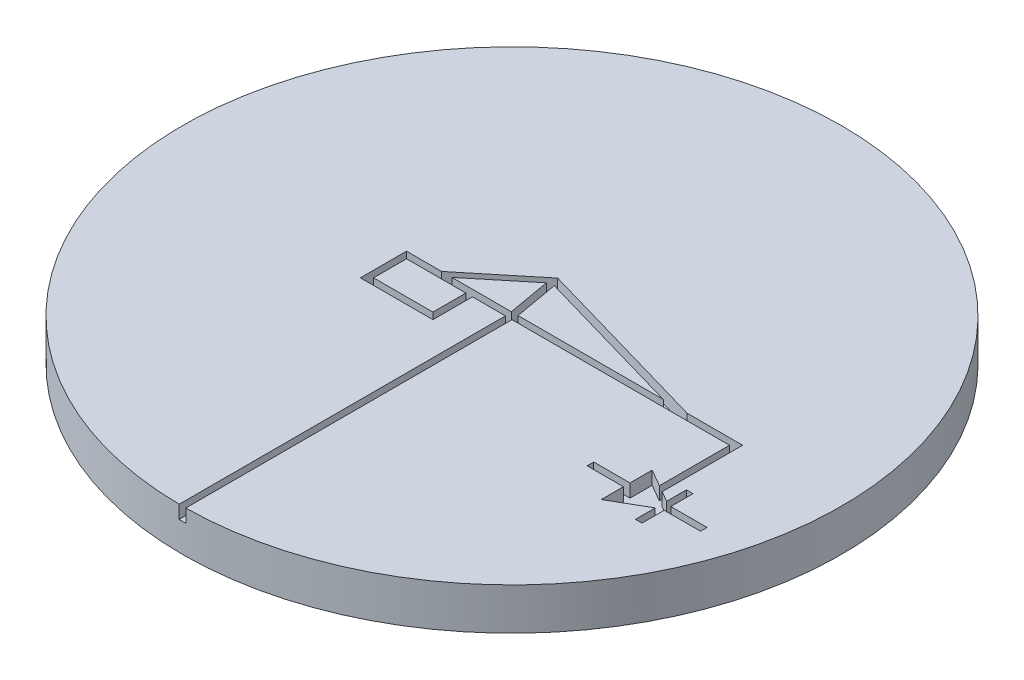
SolidWorks part; units mm, degrees
material "ABS PC"
ref_plane "Front Plane" through (0, 0, 0) normal (0, 0, 1) x (1, 0, 0)
ref_plane "Top Plane" through (0, 0, 0) normal (0, 1, 0) x (1, 0, 0)
ref_plane "Right Plane" through (0, 0, 0) normal (1, 0, 0) x (0, 0, -1)
sketch "Sketch1" plane through (0, 0, 0) normal (0, 1, 0) x (1, 0, 0)
  circle A0 centre (0, 0) radius 25
  dimension "D1" = 50
extrude "Boss-Extrude1" add sketch "Sketch1" along normal blind 3.175
sketch "Sketch2" plane through (0, 3.175, 0) normal (0, 1, 0) x (1, 0, 0)
  line L0 (0, 0) -> (0, -25) construction
  line L1 (-8, 0) -> (17, 0) construction
  line L2 (0, 0) -> (-0.6946, 3.9392) construction
  line L3 (-0.6946, 3.9392) -> (-5.5, 0) construction
  line L4 (-8, 0) -> (-8, -3) construction
  line L5 (-8, -3) -> (-3, -3) construction
  line L6 (-3, -3) -> (-3, 0) construction
  line L7 (-0.6946, 3.9392) -> (13, 0) construction
  line L8 (17, 0) -> (17, -6) construction
  line L9 (18.299, -6.75) -> (15.701, -5.25) construction
  line L10 (15.701, -5.25) -> (15.701, -8.25) construction
  line L11 (15.701, -8.25) -> (18.299, -6.75) construction
  line L12 (18.299, -5.25) -> (18.299, -8.25) construction
  line L13 (18.299, -6.75) -> (21.299, -6.75) construction
  line L14 (15.701, -6.75) -> (12.701, -6.75) construction
  line L15 (17.25, 0.25) -> (17.25, -5.8557)
  line L16 (-8.25, 0.25) -> (-5.5894, 0.25)
  line L17 (-8.25, 0.25) -> (-8.25, -3.25)
  line L18 (-8.25, -3.25) -> (-2.75, -3.25)
  line L19 (-2.75, -3.25) -> (-2.75, -0.25)
  line L20 (-0.8531, 4.1326) -> (-5.5894, 0.25)
  line L21 (-0.8531, 4.1326) -> (-5.6585, 0.1933) construction
  line L22 (-4.8007, 0.25) -> (-0.2979, 0.25)
  line L23 (0.2098, 0.25) -> (-0.3789, 3.5883)
  line L25 (15.451, -4.817) -> (15.451, -6.5)
  line L26 (15.451, -8.683) -> (18.049, -7.183)
  line L27 (18.049, -5.25) -> (18.049, -6.317)
  line L28 (18.549, -7) -> (21.299, -7)
  line L29 (15.451, -6.5) -> (12.701, -6.5)
  line L30 (16.75, -0.25) -> (16.75, -5.567)
  line L31 (-7.75, -0.25) -> (-3.25, -0.25)
  line L32 (-7.75, -0.25) -> (-7.75, -2.75)
  line L33 (-7.75, -2.75) -> (-3.25, -2.75)
  line L34 (-3.25, -2.75) -> (-3.25, -0.25)
  line L35 (-0.8531, 4.1326) -> (-0.7516, 4.2158)
  line L36 (-0.6255, 4.1795) -> (13.0352, 0.25)
  line L37 (-0.25, -0.25) -> (-0.25, -24.9987)
  line L38 (-8.25, 0.25) -> (17.25, 0.25) construction
  line L42 (18.549, -5.25) -> (18.549, -6.5)
  line L43 (18.549, -6.5) -> (21.299, -6.5)
  line L44 (15.451, -7) -> (12.701, -7)
  line L45 (-0.6255, 4.1795) -> (-0.7516, 4.2158)
  line L46 (-0.6255, 4.1795) -> (13.0691, 0.2403) construction
  line L47 (-0.8666, 3.475) -> (-4.8007, 0.25)
  line L48 (-0.3789, 3.5883) -> (11.2265, 0.25)
  line L49 (-0.25, -0.0219) -> (-0.9408, 3.8958) construction
  line L50 (0.25, 0.0219) -> (-0.4484, 3.9826) construction
  line L51 (-3.25, -2.75) -> (-3.25, 0) construction
  line L52 (-2.75, -3.25) -> (-2.75, 0) construction
  line L53 (-0.2979, 0.25) -> (-0.8666, 3.475)
  line L54 (0.25, -0.25) -> (0.25, -24.9987)
  line L55 (0.25, 0.0219) -> (0.25, -25) construction
  line L56 (-0.25, -0.0219) -> (-0.25, -25) construction
  line L57 (13.0352, 0.25) -> (17.25, 0.25)
  line L58 (-2.75, -0.25) -> (-0.25, -0.25)
  line L59 (-7.75, -0.25) -> (16.75, -0.25) construction
  line L60 (0.2098, 0.25) -> (11.2265, 0.25)
  line L61 (16.75, -0.25) -> (16.75, -6) construction
  line L62 (17.25, 0.25) -> (17.25, -6) construction
  line L63 (18.049, -7.183) -> (18.049, -8.25)
  line L64 (18.049, -5.25) -> (18.049, -8.25) construction
  line L65 (18.299, -6.5) -> (21.299, -6.5) construction
  line L66 (18.299, -7) -> (21.299, -7) construction
  line L67 (18.799, -6.75) -> (15.451, -4.817) construction
  line L68 (15.451, -8.683) -> (18.799, -6.75) construction
  line L69 (18.549, -7) -> (18.549, -8.25)
  line L70 (18.549, -5.25) -> (18.549, -8.25) construction
  line L71 (18.049, -6.317) -> (17.25, -5.8557)
  line L72 (15.451, -7) -> (15.451, -8.683)
  line L73 (15.451, -4.817) -> (15.451, -8.683) construction
  line L74 (15.701, -7) -> (12.701, -7) construction
  line L75 (15.701, -6.5) -> (12.701, -6.5) construction
  line L76 (12.701, -7) -> (12.701, -6.5)
  line L77 (18.049, -8.25) -> (18.049, -8.683)
  line L78 (18.049, -8.683) -> (18.549, -8.683)
  line L79 (18.549, -8.683) -> (18.549, -8.25)
  line L80 (18.049, -5.25) -> (18.049, -4.817)
  line L81 (18.049, -4.817) -> (18.549, -4.817)
  line L82 (18.549, -4.817) -> (18.549, -5.25)
  line L83 (21.299, -6.5) -> (21.299, -7)
  line L84 (16.75, -5.567) -> (15.451, -4.817)
  line L85 (0.25, -0.25) -> (16.75, -0.25)
  circle A0 centre (0, 0) radius 25 construction
  arc A1 (-0.25, -24.9987) -> (0.25, -24.9987) centre (0, 0) ccw
  point P13 (-5.5, -3)
  point P25 (17, -6)
  dimension "D1" = 3
  dimension "D2" = 5
  dimension "D3" = 8
  dimension "D4" = 4
  dimension "D5" = 80
  dimension "D6" = 4
  dimension "D7" = 3
  dimension "D8" = 6
  dimension "D9" = 3
  dimension "D10" = 17
  dimension "D11" = 0.25
  dimension "D12" = 0.25
extrude "Cut-Extrude1" cut sketch "Sketch2" against normal blind 1
